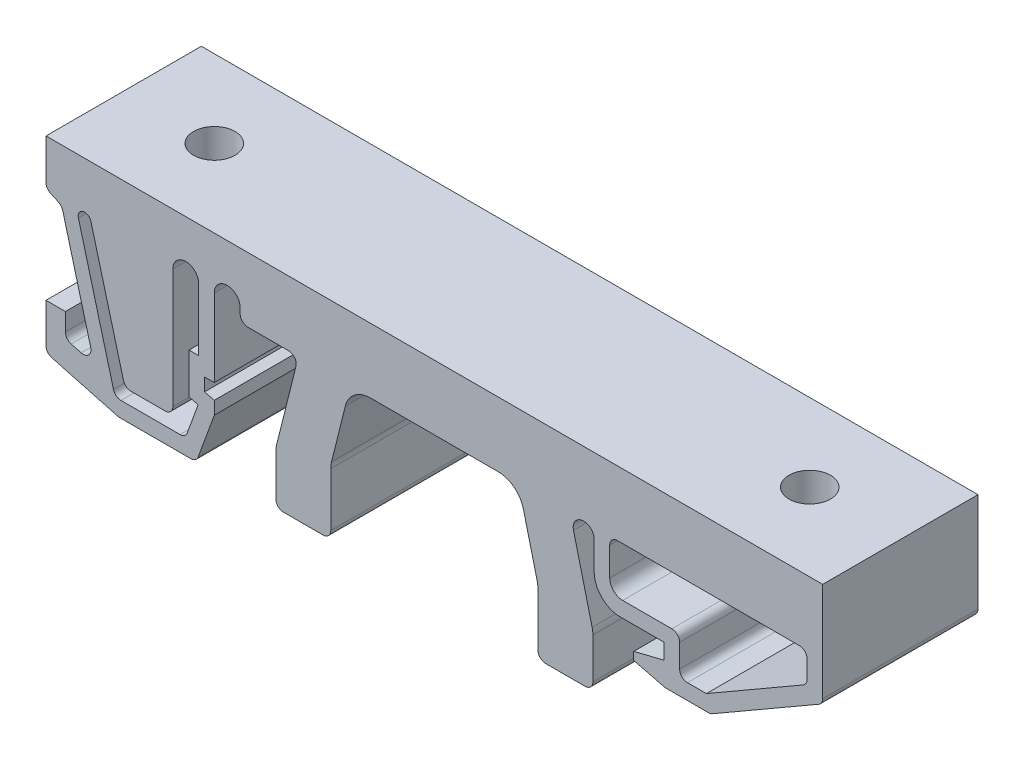
SolidWorks part; units mm, degrees
ref_plane "Front Plane" through (0, 0, 0) normal (0, 0, 1) x (1, 0, 0)
ref_plane "Top Plane" through (0, 0, 0) normal (0, 1, 0) x (1, 0, 0)
ref_plane "Right Plane" through (0, 0, 0) normal (1, 0, 0) x (0, 0, -1)
sketch "Sketch2" plane through (0, 0, 0) normal (0, 0, 1) x (1, 0, 0)
  line L0 (0, 22.5226) -> (0, -8.8845) construction
  line L1 (6.5, 11) -> (-6.5, 11)
  line L2 (-6.5, 11) -> (-8, 4.9838)
  line L3 (-8, 4.9838) -> (-8, 0)
  line L4 (-8, 0) -> (-12.25, 0)
  line L5 (-12.25, 0) -> (-12.25, 3.9811)
  line L6 (-12.25, 3.9811) -> (-10.5, 11)
  line L7 (-10.5, 11) -> (-15, 11)
  line L8 (-15, 11) -> (-15, 13)
  line L9 (-15, 13) -> (-17, 13)
  line L10 (-17, 13) -> (-17, 6)
  line L11 (-17, 6) -> (-17.75, 6)
  line L12 (-17.75, 6) -> (-17.75, 5)
  line L13 (-17.75, 5) -> (-17, 4.813)
  line L14 (-17, 4.813) -> (-17, 3.813)
  line L15 (-17, 3.813) -> (-18.3878, 0)
  line L16 (-18.3878, 0) -> (-24.3878, 0)
  line L17 (-24.3878, 0) -> (-30, 1.5038)
  line L18 (-30, 1.5038) -> (-30, 5.0038)
  line L19 (-30, 5.0038) -> (-28.5, 5.0038)
  line L20 (-28.5, 5.0038) -> (-28.5, 3.1724)
  line L21 (-28.5, 3.1724) -> (-26.2784, 2.5771)
  line L22 (-26.2784, 2.5771) -> (-28.7854, 11.9336)
  line L23 (-28.7854, 11.9336) -> (-30, 12.5)
  line L24 (-30, 12.5) -> (-30, 16)
  line L25 (-30, 16) -> (0, 16)
  line L30 (-8, 0) -> (0, 0) construction
  line L32 (10.5, 11) -> (12.35, 11)
  line L33 (12.25, 3.9811) -> (10.5, 11)
  line L34 (12.25, 0) -> (12.25, 3.9811)
  line L35 (8, 0) -> (12.25, 0)
  line L36 (8, 4.9838) -> (8, 0)
  line L37 (6.5, 11) -> (8, 4.9838)
  line L38 (12.35, 11) -> (12.35, 6)
  line L40 (12.35, 6) -> (17.75, 6)
  line L41 (17.75, 6) -> (17.75, 4.8)
  line L42 (17.75, 4.8) -> (15.4, 4.2141)
  line L43 (15.4, 4.2141) -> (15.4, 3.6083)
  line L44 (15.4, 3.6083) -> (17.8397, 3)
  line L45 (17.8397, 3) -> (21.3397, 3)
  line L46 (21.3397, 3) -> (30, 8)
  line L47 (30, 8) -> (30, 16)
  line L48 (30, 16) -> (0, 16)
  line L49 (-17.75, 6) -> (0, 6) construction
  line L50 (0, 6) -> (17.75, 6) construction
  line L54 (15.4, 3.9112) -> (22.918, 3.9112) construction
  line L56 (-8, 0) -> (8, 0) construction
  point P37 (0, 11)
  dimension "D1" = 5
  dimension "D2" = 16
  dimension "D3" = 104
  dimension "D4" = 16
  dimension "D5" = 13
  dimension "D6" = 24.5
  dimension "D7" = 4
  dimension "D8" = 2
  dimension "D9" = 2
  dimension "D10" = 4.5
  dimension "D11" = 35.5
  dimension "D12" = 7
  dimension "D13" = 1
  dimension "D14" = 1
  dimension "D15" = 20
  dimension "D16" = 6
  dimension "D17" = 15
  dimension "D18" = 1.5
  dimension "D19" = 3.5
  dimension "D20" = 2
  dimension "D21" = 60
  dimension "D22" = 60
  dimension "D23" = 50
  dimension "D24" = 3.5
  dimension "D25" = 2.3
  dimension "D26" = 60
  dimension "D27" = 8
  dimension "D28" = 15.4
  dimension "D29" = 3.5
  dimension "D30" = 1.2
  dimension "D31" = 5.4
  dimension "D32" = 3
extrude "Boss-Extrude1" add sketch "Sketch2" along normal mid plane 12
sketch "Sketch3" plane through (0, 0, 0) normal (0, 0, 1) x (1, 0, 0)
  line L0 (-27.6263, 12.2442) -> (-24.667, 1.2)
  line L1 (-24.667, 1.2) -> (-19.2281, 1.2)
  line L2 (-19.2281, 1.2) -> (-18.2498, 3.8879)
  line L3 (-18.2498, 3.8879) -> (-18.95, 4.0625)
  line L4 (-18.95, 4.0625) -> (-18.95, 7.2)
  line L5 (-18.95, 7.2) -> (-18.2, 7.2)
  line L6 (-18.2, 7.2) -> (-18.2, 13)
  line L7 (-18.2, 13) -> (-20.2, 13)
  line L8 (-20.2, 13) -> (-20.2, 2.2)
  line L9 (-20.2, 2.2) -> (-23.8997, 2.2)
  line L10 (-23.8997, 2.2) -> (-26.6604, 12.503)
  line L11 (-26.6604, 12.503) -> (-27.6263, 12.2442)
  line L12 (13.55, 11) -> (13.55, 7.2)
  line L13 (13.55, 7.2) -> (18.95, 7.2)
  line L14 (18.95, 7.2) -> (18.95, 4.2)
  line L15 (18.95, 4.2) -> (21.0182, 4.2)
  line L16 (21.0182, 4.2) -> (28.8, 8.6928)
  line L17 (28.8, 8.6928) -> (28.8, 11)
  line L18 (28.8, 11) -> (13.55, 11)
  line L19 (-28.7854, 11.9336) -> (-26.2784, 2.5771) construction
  line L20 (-18.3878, 0) -> (-17, 3.813) construction
  line L21 (-24.3878, 0) -> (-18.3878, 0) construction
  line L22 (-17.75, 5) -> (-17.75, 6) construction
  line L23 (-17, 6) -> (-17, 13) construction
  line L26 (-17, 4.813) -> (-17.75, 5) construction
  line L27 (-17.75, 6) -> (-17, 6) construction
  line L28 (-17, 13) -> (-15, 13) construction
  line L29 (12.35, 11) -> (12.35, 6) construction
  line L30 (12.35, 6) -> (17.75, 6) construction
  line L31 (17.75, 6) -> (17.75, 4.8) construction
  line L32 (30, 8) -> (30, 16) construction
  line L33 (21.3397, 3) -> (30, 8) construction
  line L34 (17.8397, 3) -> (21.3397, 3) construction
  line L35 (10.5, 11) -> (12.35, 11) construction
  point P23 (-26.0206, 12.5114)
  dimension "D1" = 1.2
  dimension "D2" = 1.2
  dimension "D3" = 1.2
  dimension "D4" = 1.2
  dimension "D5" = 1.2
  dimension "D6" = 2
  dimension "D7" = 1
  dimension "D8" = 1.2
  dimension "D9" = 1.2
  dimension "D10" = 1.2
  dimension "D11" = 1.2
  dimension "D12" = 1.2
  dimension "D13" = 1.2
  dimension "D14" = 1.2
  dimension "D15" = 1.2
  dimension "D16" = 1
extrude "Cut-Extrude1" cut sketch "Sketch3" against normal through all both and the other way through all
fillet "Fillet1" radius 2 1 edges at (12.35, 6, 0)
fillet "Fillet2" radius 1 1 edges at (13.55, 7.2, 0)
fillet "Fillet3" 2 edges at (10.5, 11, 0) (12.35, 11, 0) type full round first side face at (11.375, 7.4906, 0) second side face at (12.35, 9.5, 0) middle face at (11.425, 11, 0)
fillet "Fillet4" radius 2 6 edges at (-12.25, 3.9811, 0) (12.25, 3.9811, 0) (8, 4.9838, 0) (-8, 4.9838, 0) (-6.5, 11, 0) (6.5, 11, 0)
fillet "Fillet5" 2 edges at (-20.2, 13, 0) (-18.2, 13, 0) type full round first side face at (-20.2, 7.6, 0) second side face at (-18.2, 10.1, 0) middle face at (-19.2, 13, 0)
fillet "Fillet6" 2 edges at (-17, 13, 0) (-15, 13, 0) type full round first side face at (-17, 9.5, 0) second side face at (-15, 12, 0) middle face at (-16, 13, 0)
fillet "Fillet7" 2 edges at (-27.6263, 12.2442, 0) (-26.6604, 12.503, 0) type full round first side face at (-26.1467, 6.7221, 0) second side face at (-25.2801, 7.3515, 0) middle face at (-27.1434, 12.3736, 0)
fillet "Fillet8" radius 0.6 25 edges at (-10.5, 11, 0) (-12.25, 0, 0) (-8, 0, 0) (8, 0, 0) (12.25, 0, 0) (17.8397, 3, 0) (28.8, 8.6928, 0) (28.8, 11, 0) (13.55, 11, 0) (18.95, 7.2, 0) (18.95, 4.2, 0) (21.3397, 3, 0) (30, 8, 0) (-23.8997, 2.2, 0) (-20.2, 2.2, 0) (-30, 1.5038, 0) (-28.5, 3.1724, 0) (-26.2784, 2.5771, 0) (-24.667, 1.2, 0) (-19.2281, 1.2, 0) (-24.3878, 0, 0) (-18.3878, 0, 0) (-15, 11, 0) (-30, 12.5, 0) (-28.7854, 11.9336, 0)
sketch "Sketch4" plane through (0, 16, 0) normal (0, 1, 0) x (1, 0, 0)
  line L0 (0, 0) -> (-23, 0) construction
  line L3 (0, 0) -> (0, -6) construction
  line L4 (30, -6) -> (-30, -6) construction
  circle A0 centre (-23, 0) radius 1.6
  circle A1 centre (23, 0) radius 1.6
  dimension "D1" = 3.2
  dimension "D2" = 46
extrude "Cut-Extrude2" cut sketch "Sketch4" against normal blind 8.5
